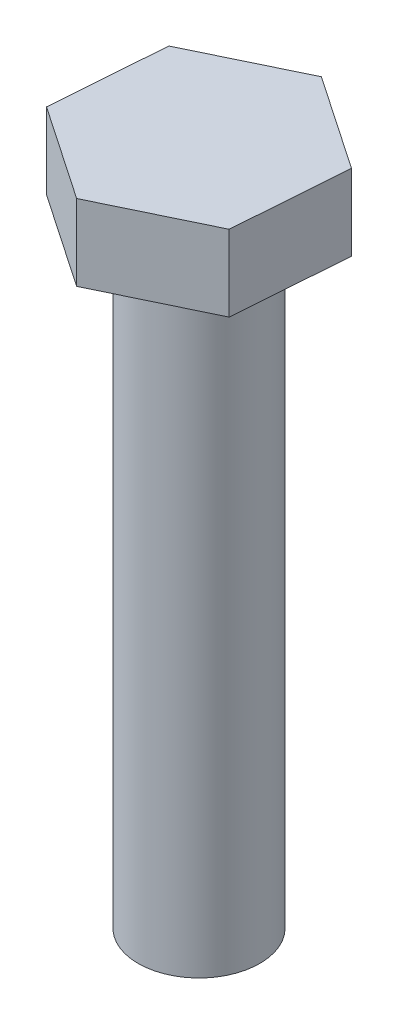
SolidWorks part; units mm, degrees
ref_plane "Front Plane" through (0, 0, 0) normal (0, 0, 1) x (1, 0, 0)
ref_plane "Top Plane" through (0, 0, 0) normal (0, 1, 0) x (1, 0, 0)
ref_plane "Right Plane" through (0, 0, 0) normal (1, 0, 0) x (0, 0, -1)
sketch "Sketch2" plane through (0, 0, 0) normal (0, 1, 0) x (1, 0, 0)
  circle A0 centre (0, 0) radius 4
  circle A1 centre (0, 0) radius 6.5
  dimension "D1" = 13
  dimension "D2" = 8
extrude "Boss-Extrude1" add sketch "Sketch2" along normal blind 5 contours A1
extrude "Boss-Extrude2" add sketch "Sketch2<3>" against normal blind 40 contours A0 region at (0, 0, 0)
sketch "Sketch2<3>" plane through (0, 0, 0) normal (0, 1, 0) x (1, 0, 0) same geometry as "Sketch2"
sketch "Sketch3" plane through (0, 0, 0) normal (0, 1, 0) x (1, 0, 0)
  line L1 (-6.7605, -3.2603) -> (-0.5568, -7.4849)
  line L2 (-0.5568, -7.4849) -> (6.2037, -4.2246)
  line L3 (6.2037, -4.2246) -> (6.7605, 3.2603)
  line L4 (6.7605, 3.2603) -> (0.5568, 7.4849)
  line L5 (0.5568, 7.4849) -> (-6.2037, 4.2246)
  line L6 (-6.2037, 4.2246) -> (-6.7605, -3.2603)
  circle A0 centre (0, 0) radius 6.5 construction
extrude "Boss-Extrude3" add sketch "Sketch3" along normal blind 5
